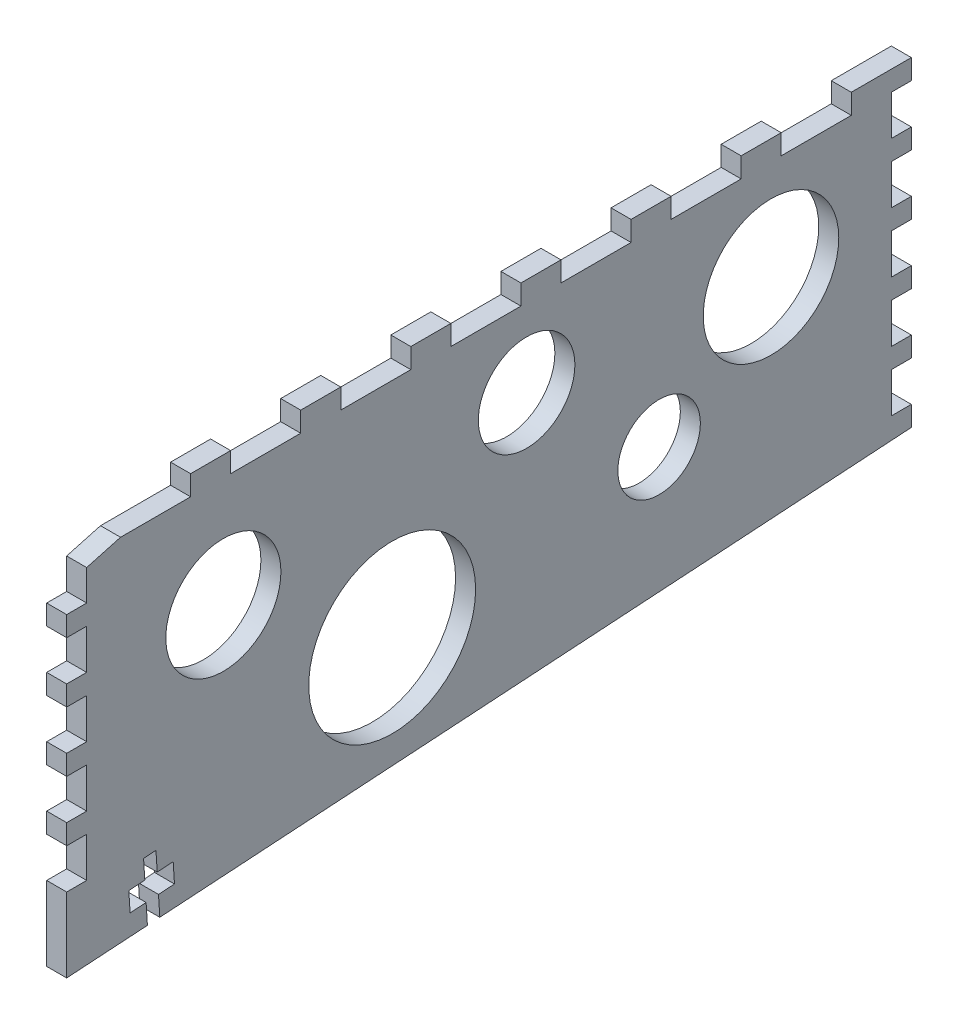
SolidWorks part; units mm, degrees
ref_plane "Plan de face" through (0, 0, 0) normal (0, 0, 1) x (1, 0, 0)
ref_plane "Plan de dessus" through (0, 0, 0) normal (0, 1, 0) x (1, 0, 0)
ref_plane "Plan de droite" through (0, 0, 0) normal (1, 0, 0) x (0, 0, -1)
sketch "Esquisse1" plane through (163.9335, 0, 0) normal (1, 0, 0) x (0, 0, -1)
  line L0 (-505.4502, 63.9129) -> (-505.4502, 78.9129) construction
  line L1 (-294.5, -14.6875) -> (-505.4502, -14.6875)
  line L2 (-294.5, -14.6875) -> (-294.5, 78.9129)
  line L3 (-294.5, 78.9129) -> (-505.4502, 78.9129)
  line L4 (-505.4502, -14.6875) -> (-505.4502, 78.9129)
  line L5 (-294.5, 33.9129) -> (-294.5, 43.9129) construction
  line L6 (-505.4502, -14.6875) -> (-500.4502, -14.6875) construction
  line L7 (-382, 78.9129) -> (-364.5, 78.9129) construction
extrude "Boss.-Extru.1" add sketch "Esquisse1" against normal blind 5
sketch "Esquisse3" plane through (163.9335, 0, 0) normal (1, 0, 0) x (0, 0, -1)
  line L0 (-505.4502, -14.6875) -> (-294.5, -1.0871)
  line L2 (-294.5, -14.6875) -> (-294.5, 78.9129) construction
  line L3 (-294.5, -1.1404) -> (-294.5, -14.6875)
  line L4 (-294.5, -14.6875) -> (-505.4502, -14.6875)
  line L5 (-294.5, -1.1404) -> (-294.5, -1.0871)
  line L7 (-503.9594, -16.1458) -> (-294.5, -1.0871) construction
extrude "Enlèv. mat.-Extru.1" cut sketch "Esquisse3" against normal blind 5
sketch "Esquisse4" plane through (163.9335, 0, 0) normal (1, 0, 0) x (0, 0, -1)
  line L0 (-294.5, -1.0871) -> (-294.5, 78.9129) construction
  line L1 (-299.5, 13.9129) -> (-294.5, 13.9129)
  line L2 (-299.5, 13.9129) -> (-299.5, 3.9129)
  line L3 (-299.5, 3.9129) -> (-294.5, 3.9129)
  line L4 (-294.5, 13.9129) -> (-294.5, 3.9129)
  line L5 (-294.5, 3.9129) -> (-299.5, 3.9129) construction
extrude "Enlèv. mat.-Extru.2" cut sketch "Esquisse4" against normal blind 5
pattern_linear "Répétition linéaire1" count 5 spacing 15 along (0, 1, 0) of "Enlèv. mat.-Extru.2"
sketch "Esquisse5" plane through (163.9335, 0, 0) normal (1, 0, 0) x (0, 0, -1)
  line L0 (-294.5, 78.9129) -> (-505.4502, 78.9129) construction
  line L1 (-309.5, 73.9129) -> (-327, 73.9129)
  line L2 (-309.5, 73.9129) -> (-309.5, 78.9129)
  line L3 (-309.5, 78.9129) -> (-327, 78.9129)
  line L4 (-327, 73.9129) -> (-327, 78.9129)
  line L5 (-327, 73.9129) -> (-327, 78.9129) construction
  point P7 (-327, 78.9129)
extrude "Enlèv. mat.-Extru.3" cut sketch "Esquisse5" against normal blind 5
pattern_linear "Répétition linéaire2" count 7 spacing 27.5 along (0, 0, 1) of "Enlèv. mat.-Extru.3"
sketch "Esquisse6" plane through (163.9335, 0, 0) normal (1, 0, 0) x (0, 0, -1)
  line L0 (-492, 73.9129) -> (-505.4502, 70.2141)
  line L1 (-505.4502, 78.9129) -> (-505.4502, -14.6875) construction
  line L2 (-505.4502, 70.2141) -> (-505.4502, 78.9129)
  line L3 (-505.4502, 78.9129) -> (-492, 78.9129)
  line L4 (-492, 78.9129) -> (-492, 73.9129)
extrude "Enlèv. mat.-Extru.4" cut sketch "Esquisse6" against normal blind 5
sketch "Esquisse8" plane through (163.9335, 0, 0) normal (1, 0, 0) x (0, 0, -1)
  circle A0 centre (-357.4954, 26.1666) radius 10.3035
  circle A1 centre (-329.5521, 48.9806) radius 16.9246
  circle A2 centre (-390.5852, 54.4911) radius 12.058
  circle A3 centre (-424.1609, 18.322) radius 20.8404
  circle A4 centre (-466.3187, 46.4356) radius 14.375
extrude "Enlèv. mat.-Extru.5" cut sketch "Esquisse8" against normal blind 5
ref_plane "Plan1" through (0, 0, 399.9751) normal (0, 0, -1) x (-1, 0, 0)
mirror "Symétrie1" about plane through (0, 0, 399.9751) normal (0, 0, -1) of "Répétition linéaire1"
ref_axis "Axe1" through (161.4335, -14.4655, 483.6797) along (0, -0.9974, -0.0717)
sketch "Esquisse9" plane through (0, 17.8258, 1.1493) normal (0, -0.9979, -0.0643) x (1, 0, 0)
  line L0 (163.9335, 293.9598) -> (163.9335, 505.348) construction
  line L1 (163.9335, 485.1387) -> (158.9335, 485.1387)
  line L2 (163.9335, 485.1387) -> (163.9335, 482.0387)
  line L3 (163.9335, 482.0387) -> (158.9335, 482.0387)
  line L4 (158.9335, 485.1387) -> (158.9335, 482.0387)
  line L5 (158.9335, 293.9598) -> (158.9335, 505.348) construction
  line L6 (163.9335, 482.0387) -> (158.9335, 485.1387) construction
  point P10 (161.4335, 483.5887)
  dimension "D1" = 3.1
extrude "Enlèv. mat.-Extru.6" cut sketch "Esquisse9" against normal blind 15
sketch "Esquisse10" plane through (163.9335, 0, 0) normal (1, 0, 0) x (0, 0, -1)
  line L0 (-485.6126, -8.2716) -> (-489.6043, -8.5289)
  line L1 (-486.2479, 1.5817) -> (-485.2828, -13.3872) construction
  line L2 (-489.6043, -8.5289) -> (-489.926, -3.5393)
  line L3 (-489.926, -3.5393) -> (-485.9343, -3.282)
  line L4 (-485.9343, -3.282) -> (-485.6126, -8.2716)
  line L5 (-485.2828, -13.3872) -> (-505.4502, -14.6875) construction
  dimension "D1" = 4
  dimension "D2" = 5
extrude "Enlèv. mat.-Extru.7" cut sketch "Esquisse10" against normal blind 15
ref_plane "Plan2" through (0, -31.1133, 482.5867) normal (0, 0.0643, -0.9979) x (-1, 0, 0)
mirror "Symétrie2" about plane through (0, -31.1133, 482.5867) normal (0, 0.0643, -0.9979) of "Enlèv. mat.-Extru.7"
